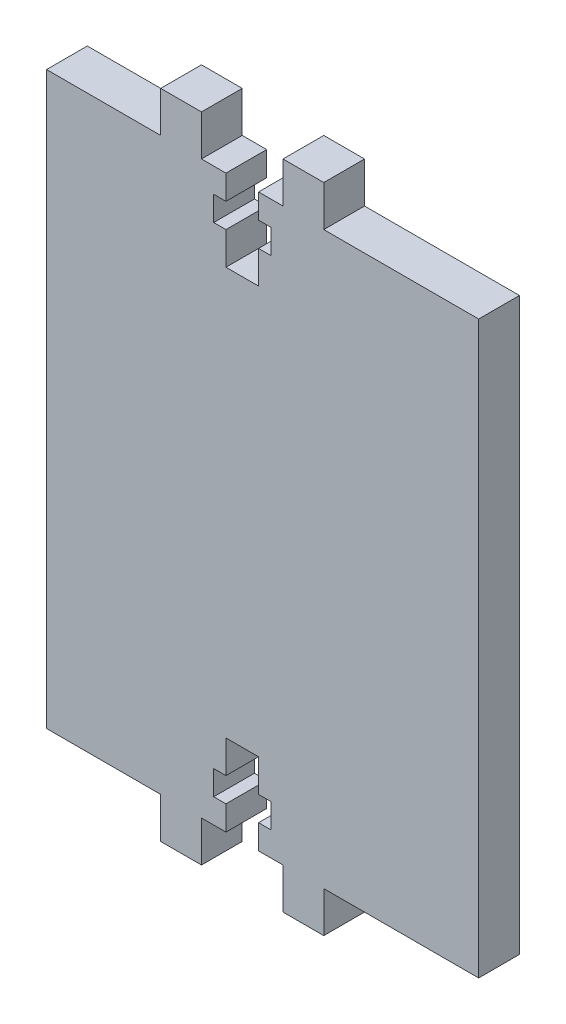
SolidWorks part; units mm, degrees
ref_plane "Plan de face" through (0, 0, 0) normal (0, 0, 1) x (1, 0, 0)
ref_plane "Plan de dessus" through (0, 0, 0) normal (0, 1, 0) x (1, 0, 0)
ref_plane "Plan de droite" through (0, 0, 0) normal (1, 0, 0) x (0, 0, -1)
sketch "Esquisse2" plane through (0, 0, 0) normal (0, 0, 1) x (1, 0, 0)
  line L0 (-10, 0) -> (-24, 0)
  line L1 (-24, 0) -> (-24, 70)
  line L2 (-24, 70) -> (29, 70) construction
  line L3 (29, 70) -> (29, 0)
  line L4 (29, 0) -> (10, 0)
  line L5 (0, 0) -> (0, 70) construction
  line L6 (-23.359, 35) -> (29, 35) construction
  line L7 (-10, 70) -> (-24, 70)
  line L8 (29, 70) -> (10, 70)
  point P12 (29, 26.1899)
  point P15 (-24, 58.5139)
  point P16 (0, 0)
  line B0 (-3.5, 3) -> (-3.5, 6)
  line B1 (2, 6) -> (2, 10)
  line B2 (-2, 10) -> (-2, 6)
  line B3 (-3.5, 6) -> (-2, 6)
  line B4 (0, 0) -> (0, 11.2208) construction
  line B5 (-2, 0) -> (-5, 0)
  line B6 (-5, -5) -> (-10, -5)
  line B7 (-10, -5) -> (-10, 0)
  line B8 (-5, -5) -> (-5, 0)
  line B9 (2, 0) -> (5, 0)
  line B10 (5, 0) -> (5, -5)
  line B11 (5, -5) -> (10, -5)
  line B12 (10, -5) -> (10, 0)
  line B13 (-2, 0) -> (2, 0) construction
  line B14 (2, 0) -> (2, 3)
  line B15 (2, 6) -> (3.5, 6)
  line B16 (3.5, 3) -> (2, 3)
  line B17 (2, 10) -> (-2, 10)
  line B18 (-2, 3) -> (-3.5, 3)
  line B19 (3.5, 6) -> (3.5, 3)
  line B20 (-2, 3) -> (-2, 0)
  line B21 (0, 10) -> (0, 0) construction
  line B22 (-3.5, 67) -> (-3.5, 64)
  line B23 (2, 64) -> (2, 60)
  line B24 (-2, 60) -> (-2, 64)
  line B25 (-3.5, 64) -> (-2, 64)
  line B26 (0, 70) -> (0, 58.7792) construction
  line B27 (-2, 70) -> (-5, 70)
  line B28 (-5, 75) -> (-10, 75)
  line B29 (-10, 75) -> (-10, 70)
  line B30 (-5, 75) -> (-5, 70)
  line B31 (2, 70) -> (5, 70)
  line B32 (5, 70) -> (5, 75)
  line B33 (5, 75) -> (10, 75)
  line B34 (10, 75) -> (10, 70)
  line B35 (-2, 70) -> (2, 70) construction
  line B36 (2, 70) -> (2, 67)
  line B37 (2, 64) -> (3.5, 64)
  line B38 (3.5, 67) -> (2, 67)
  line B39 (2, 60) -> (-2, 60)
  line B40 (-2, 67) -> (-3.5, 67)
  line B41 (3.5, 64) -> (3.5, 67)
  line B42 (-2, 67) -> (-2, 70)
  line B43 (0, 60) -> (0, 70) construction
  dimension "D1" = 24
  dimension "D2" = 29
  dimension "D3" = 70
sketch_block_instance "Insert M4 plots ep 5mm-1"
sketch_block "Insert M4 plots ep 5mm" parameters "D1"=10, "D2"=5, "D3"=5, "D4"=7, "D5"=4, "D6"=3, "D7"=3, "D8"=10
sketch_block_instance "Insert M4 plots ep 5mm-3"
extrude "Boss.-Extru.1" add sketch "Esquisse2" along normal blind 5 contours B40 B42 B27 B30 B28 B29 L7 L1 L0 B7 B6 B8 B5 B20 B18 B0 B3 B2 B17 B1 B15 B19 B16 B14 B9 B10 B11 B12 L4 L3 L8 B34 B33 B32 B31 B36 B38 B41 B37 B23 B39 B24 B25 B22 region at (2.4987, 35, 0)
